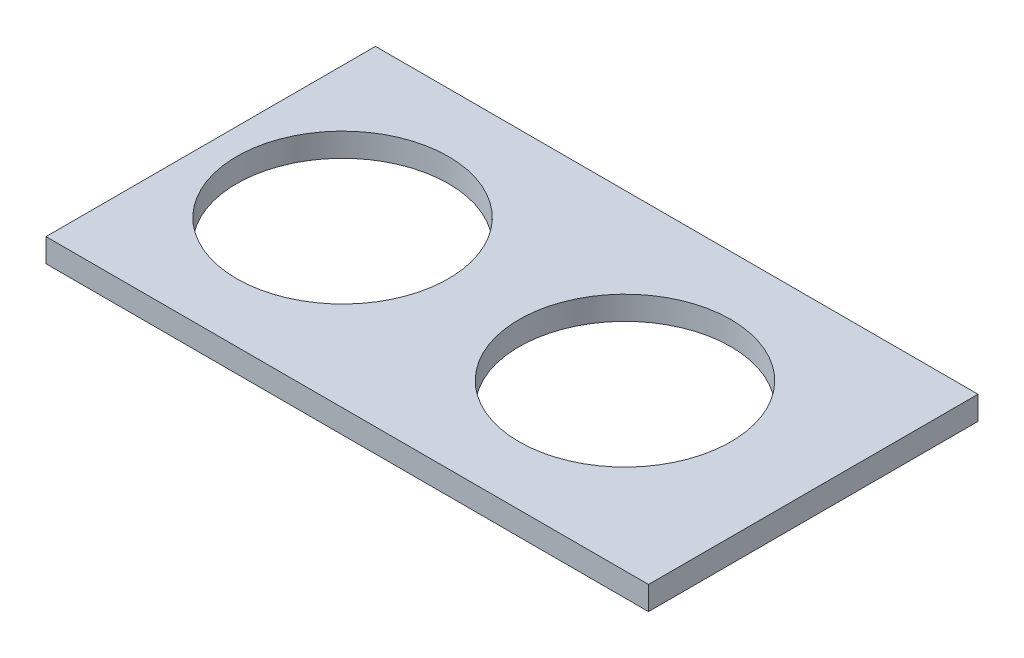
SolidWorks part; units mm, degrees
ref_plane "Front Plane" through (0, 0, 0) normal (0, 0, 1) x (1, 0, 0)
ref_plane "Top Plane" through (0, 0, 0) normal (0, 1, 0) x (1, 0, 0)
ref_plane "Right Plane" through (0, 0, 0) normal (1, 0, 0) x (0, 0, -1)
sketch "Sketch1" plane through (0, 0, 0) normal (0, 1, 0) x (1, 0, 0)
  line L1 (-17.78, -22.225) -> (63.5, -22.225)
  line L2 (-17.78, -22.225) -> (-17.78, 22.225)
  line L3 (-17.78, 22.225) -> (63.5, 22.225)
  line L4 (63.5, -22.225) -> (63.5, 22.225)
  line L5 (-17.78, -22.225) -> (63.5, 22.225) construction
  line L6 (-17.78, 22.225) -> (63.5, -22.225) construction
  circle A0 centre (0, 0) radius 11.43 construction
  circle A2 centre (38.1, 0) radius 26.67 construction
  circle A3 centre (0, 0) radius 14.2875
  circle A4 centre (38.1, 0) radius 14.2875
  point P4 (22.86, 0)
  dimension "D1" = 22.86
  dimension "D2" = 53.34
  dimension "D3" = 6.35
  dimension "D5" = 28.575
  dimension "D4" = 63.5
  dimension "D6" = 44.45
extrude "Boss-Extrude1" add sketch "Sketch1" along normal blind 3.175 contours L1 L4 L3 L2 A4 A3 region at (-16.8536, 0, 0)
